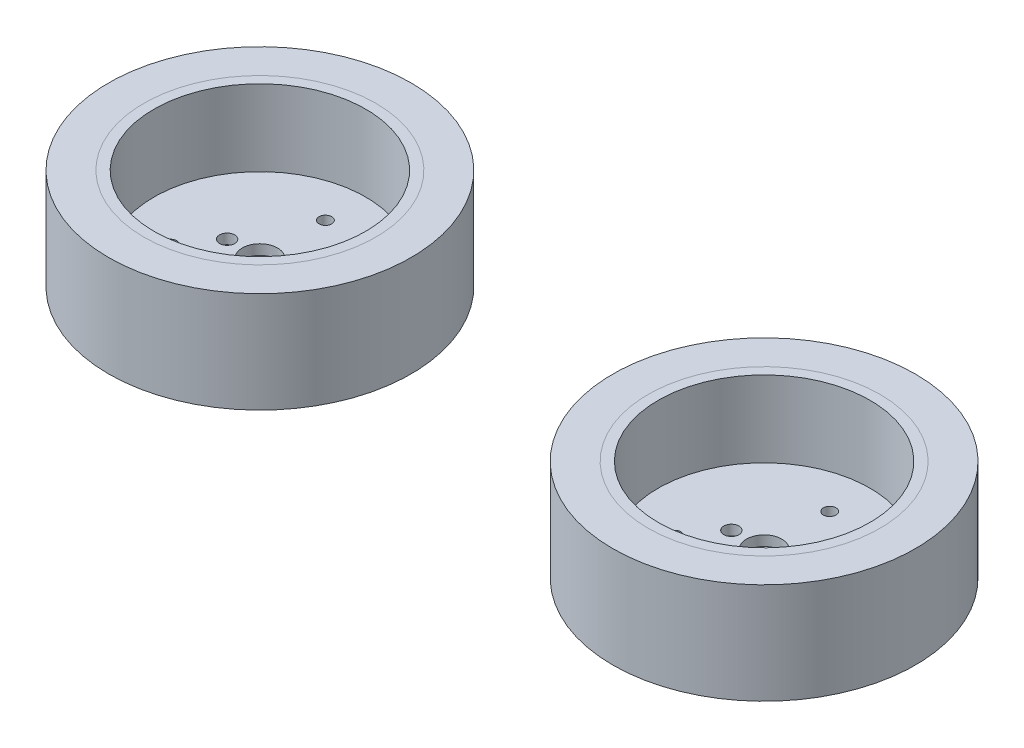
SolidWorks part; units mm, degrees
ref_plane "前视基准面" through (0, 0, 0) normal (0, 0, 1) x (1, 0, 0)
ref_plane "上视基准面" through (0, 0, 0) normal (0, 1, 0) x (1, 0, 0)
ref_plane "右视基准面" through (0, 0, 0) normal (1, 0, 0) x (0, 0, -1)
sketch "草图1" plane through (0, 0, 0) normal (0, 0, 1) x (1, 0, 0)
  line L0 (-19.1985, -10.5) -> (-10, -19.6985)
  line L5 (-19.1985, -10.5) -> (-25, -10.5)
  line L6 (-50, -32) -> (50, -32) construction
  line L7 (-50, 37) -> (-50, -32) construction
  line L8 (-27, 10) -> (-20, 10)
  line L9 (-27, -10) -> (-20, -10)
  line L10 (0, 0) -> (0, -32) construction
  line L11 (-50, 37) -> (50, 37) construction
  line L12 (-27, 10) -> (-27, -10)
  line L18 (-10, -19.6985) -> (-10, -25)
  line L19 (-46.5, -7.1) -> (-39.5, -7.1)
  line L28 (-34.5, -10) -> (-39.5, -10)
  line L29 (-39.5, -10) -> (-39.5, -7.1)
  line L30 (-27, 10) -> (-29, 10)
  line L31 (-29, 10) -> (-29, -5.1)
  line L32 (-29, -5.1) -> (-46.5, -5.1)
  line L33 (-25, 25) -> (25, 25)
  line L34 (-46.5, -5.1) -> (-46.5, -7.1)
  line L35 (-25, -25) -> (-10, -25)
  line L36 (-25, -10.5) -> (-25, -25)
  line L37 (-25, 10.5) -> (-25, 25)
  line L38 (0, -11) -> (0, 11) construction
  line L39 (-25, 10.5) -> (-20.182, 10.5)
  line L40 (25, -25) -> (10, -25)
  line L41 (10, -19.6985) -> (10, -25)
  line L42 (19.1985, -10.5) -> (10, -19.6985)
  line L43 (19.1985, -10.5) -> (25, -10.5)
  line L44 (25, -10.5) -> (25, -25)
  line L45 (25, 10.5) -> (25, 25)
  line L46 (25, 10.5) -> (20.182, 10.5)
  line L47 (50, -32) -> (50, 37) construction
  line L48 (-34.5, -10) -> (-34.5, -7.1)
  line L49 (-34.5, -7.1) -> (-29, -7.1)
  line L50 (-27, -10) -> (-29, -10)
  line L51 (-29, -10) -> (-29, -7.1)
  line L52 (-20, 10) -> (-20, -10)
  line L53 (-20, 0) -> (0, 0) construction
  arc A0 (20.182, 10.5) -> (-20.182, 10.5) centre (0, 0) ccw
  circle A1 centre (0, 0) radius 21 construction
  dimension "D1" = 42
  dimension "D2" = 45
  dimension "D5" = 60
  dimension "D13" = 7
  dimension "D18" = 45.5
  dimension "D9" = 25
  dimension "D3" = 100
  dimension "D4" = 20
  dimension "D6" = 37
  dimension "D7" = 2
  dimension "D8" = 2
  dimension "D10" = 2.9
  dimension "D11" = 50
  dimension "D12" = 32
  dimension "D14" = 42
  dimension "D15" = 21
  dimension "D16" = 50
  dimension "D17" = 0.5
  dimension "D19" = 0.5
  dimension "D20" = 20
  dimension "D21" = 5
revolve "旋转1" add sketch "草图1" angle 360 about L7 region at (-23.5, 0, 0)
revolve "旋转2" add sketch "草图1<5>" angle 360 about L7 region at (-27.2793, 0, 0)
sketch "草图1<5>" plane through (0, 0, 0) normal (0, 0, 1) x (1, 0, 0) same geometry as "草图1"
sketch "草图2" plane through (0, -7.1, 0) normal (0, -1, 0) x (-1, 0, 0)
  line L0 (43.5, 0) -> (56.5, 0) construction
  circle A0 centre (43.5, 0) radius 1.5
  circle A1 centre (56.5, 0) radius 1.5
  dimension "D2" = 3
  dimension "D1" = 13
extrude "切除-拉伸1" cut sketch "草图2" against normal through all
hole_wizard "M3 螺纹孔1" positions "草图3" profile "草图4" tap size "M3" standard "GB" end condition through all
sketch "草图3" plane through (0, -10, 0) normal (0, -1, 0) x (-1, 0, 0)
  circle A0 centre (50, 0) radius 13 construction
  circle A1 centre (50, 0) radius 15.5 construction
  point P0 (50, 13)
  point P11 (61.2583, -6.5)
  point P12 (38.7417, -6.5)
  dimension "D1" = 2.5
  dimension "D2" = 3
sketch "草图4" plane through (-50, -10, -13) normal (1, 0, 0) x (0, 0, -1)
  line L0 (0, 0) -> (0, 20)
  line L1 (0, 20) -> (1.25, 20)
  line L2 (1.25, 20) -> (1.25, 0)
  line L5 (1.25, 0) -> (0, 0)
  line L11 (0, -6.35) -> (0, 107.95) construction
  dimension "通孔螺纹孔钻头直径" = 2.5
  dimension "通孔螺纹孔钻头深度" = 20
cosmetic thread "孔螺蚊线1" parameters "D2"=3
cosmetic thread "孔螺蚊线2" parameters "D2"=3
cosmetic thread "孔螺蚊线3" parameters "D2"=3
mirror "镜向2" about plane through (0, 0, 0) normal (1, 0, 0) of bodies 106 112 124
